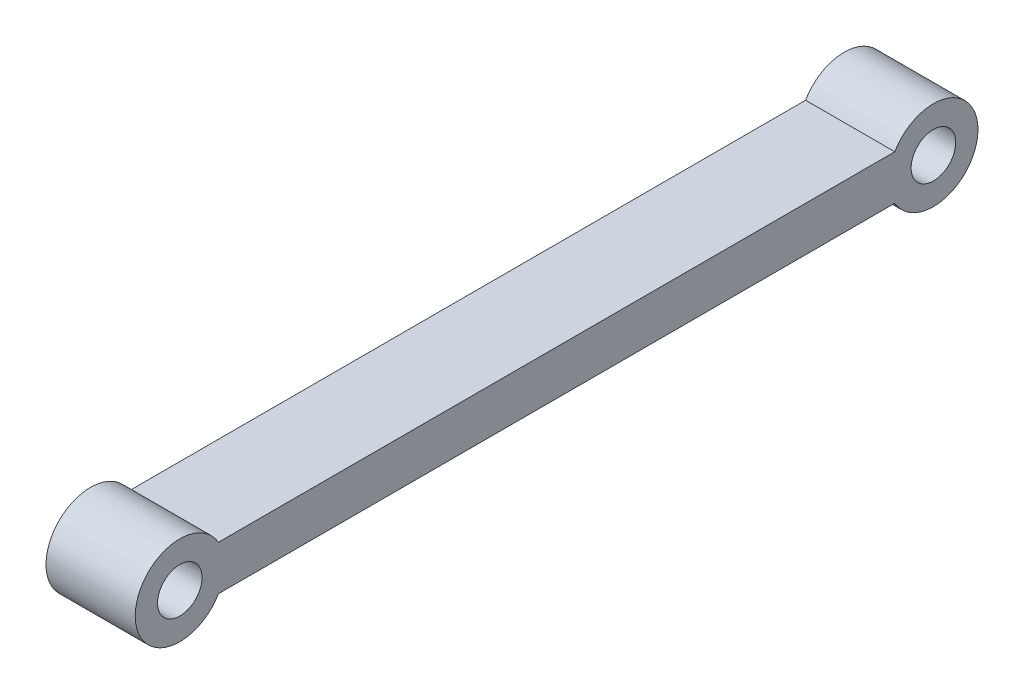
SolidWorks part; units mm, degrees
ref_plane "Front Plane" through (0, 0, 0) normal (0, 0, 1) x (1, 0, 0)
ref_plane "Top Plane" through (0, 0, 0) normal (0, 1, 0) x (1, 0, 0)
ref_plane "Right Plane" through (0, 0, 0) normal (1, 0, 0) x (0, 0, -1)
sketch "Sketch1" plane through (0, 0, 0) normal (1, 0, 0) x (0, 0, -1)
  line L1 (-15.1629, -2) -> (15.1629, -2)
  line L3 (-15.1629, 0) -> (15.1629, 0)
  arc A0 (-15.1629, 0) -> (-15.1629, -2) centre (-16.895, -1) ccw
  arc A1 (15.1629, -2) -> (15.1629, 0) centre (16.895, -1) ccw
  circle A2 centre (-16.895, -1) radius 1
  circle A3 centre (16.895, -1) radius 1
  point P0 (0, 0)
  point P1 (0, 0)
  point P3 (0, -2)
  dimension "D2" = 4
  dimension "D4" = 2
  dimension "D3" = 2
  dimension "D1" = 33.79
extrude "Boss-Extrude1" add sketch "Sketch1" along normal mid plane 4
